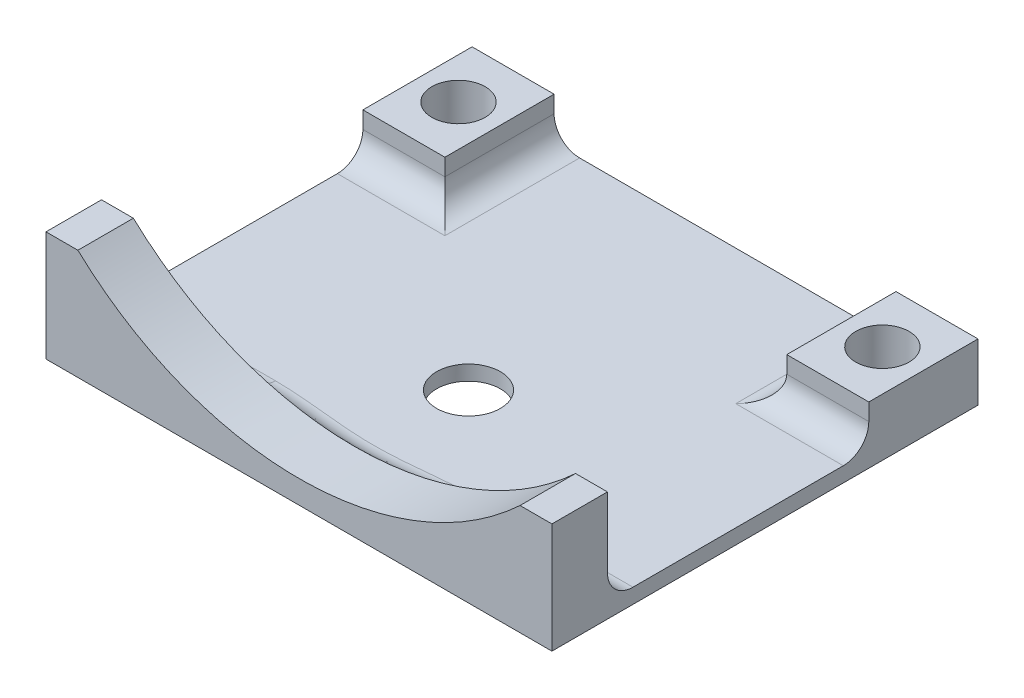
SolidWorks part; units mm, degrees
material "ABS"
ref_plane "Front Plane" through (0, 0, 0) normal (0, 0, 1) x (1, 0, 0)
ref_plane "Top Plane" through (0, 0, 0) normal (0, 1, 0) x (1, 0, 0)
ref_plane "Right Plane" through (0, 0, 0) normal (1, 0, 0) x (0, 0, -1)
sketch "Sketch1" plane through (0, 0, 0) normal (0, 1, 0) x (1, 0, 0)
  line L1 (-22.0091, -18.034) -> (22.0091, -18.034)
  line L2 (-22.0091, -18.034) -> (-22.0091, 18.034)
  line L3 (-22.0091, 18.034) -> (22.0091, 18.034)
  line L4 (22.0091, -18.034) -> (22.0091, 18.034)
  line L5 (-22.0091, -18.034) -> (22.0091, 18.034) construction
  line L6 (-22.0091, 18.034) -> (22.0091, -18.034) construction
  point P0 (0, 0)
  dimension "D1" = 44.0182
  dimension "D2" = 36.068
extrude "Boss-Extrude1" add sketch "Sketch1" along normal blind 1.4859
sketch "Sketch2" plane through (0, 0, 18.034) normal (0, 0, 1) x (1, 0, 0)
  line L0 (-22.0091, 0) -> (-22.0091, 10.9728)
  line L1 (22.0091, 0) -> (22.0091, 10.9728)
  line L2 (-22.0091, 1.4859) -> (22.0091, 1.4859) construction
  line L3 (-22.0091, 2.2987) -> (22.0091, 2.2987) construction
  line L8 (-22.0091, 0) -> (22.0091, 0)
  line L9 (22.0091, 0) -> (22.0091, 1.4859)
  line L10 (22.0091, 1.4859) -> (-22.0091, 1.4859)
  line L11 (-22.0091, 1.4859) -> (-22.0091, 0)
  line L12 (-22.0091, 0) -> (22.0091, 0)
  arc A0 (-22.0091, 10.9728) -> (22.0091, 10.9728) centre (0, 34.558) ccw
  dimension "D2" = 0.8128
  dimension "D1" = 10.9728
  dimension "D3" = 0
extrude "Boss-Extrude2" add sketch "Sketch2" against normal blind 5.5245
hole_wizard "1/4 (0.25) Diameter Hole1" positions "Sketch4" profile "Sketch3" hole size "1/4" standard "ANSI Inch"
sketch "Sketch4" plane through (0, 1.4859, 0) normal (0, 1, 0) x (1, 0, 0)
  line L0 (22.0091, 18.034) -> (-22.0091, 18.034) construction
  point P0 (0, -1.1557)
  dimension "D1" = 19.1897
sketch "Sketch3" plane through (0, 1.4859, 1.1557) normal (1, 0, 0) x (0, 0, 1)
  line L0 (0, 0) -> (0, 11.4327)
  line L1 (0, 11.4327) -> (3.175, 9.525)
  line L2 (3.175, 9.525) -> (3.175, 0)
  line L5 (3.175, 0) -> (0, 0)
  line L10 (0, 11.4327) -> (-3.175, 9.525) construction
  line L11 (0, -6.35) -> (0, 107.95) construction
  dimension "Hole Dia." = 6.35
  dimension "Hole Depth" = 9.525
  dimension "Drill Angle" = 118
sketch "Sketch5" plane through (0, 1.4859, 0) normal (0, 1, 0) x (1, 0, 0)
  line L0 (0, 18.034) -> (0, -18.034) construction
  line L1 (-22.0091, 18.034) -> (-17.018, 18.034)
  line L2 (-22.0091, 18.034) -> (-22.0091, 13.5128)
  line L3 (-22.0091, 13.5128) -> (-17.018, 13.5128)
  line L4 (-17.018, 18.034) -> (-17.018, 13.5128)
  line L5 (22.0091, 18.034) -> (-22.0091, 18.034) construction
  line L6 (-22.0091, -18.034) -> (22.0091, -18.034) construction
  line L7 (17.018, 18.034) -> (17.018, 13.5128)
  line L8 (22.0091, 13.5128) -> (17.018, 13.5128)
  line L9 (22.0091, 18.034) -> (22.0091, 13.5128)
  line L10 (22.0091, 18.034) -> (17.018, 18.034)
  line M4 (22.0091, 18.034) -> (-22.0091, 18.034)
  line M5 (-22.0091, 18.034) -> (-22.0091, -12.5095)
  dimension "D1" = 4.5212
  dimension "D2" = 4.9911
extrude "Boss-Extrude3" add sketch "Sketch5" along normal blind 5.715 from surface at -1.4859 contours L4 L3 M4 M5 | L7 L8 L9 L10 starting at face at (0, 0, -2.0193)
fillet "Fillet1" radius 2.54 5 edges at (19.5135, 1.4859, -13.5128) (17.018, 1.4859, -15.7734) (-17.018, 1.4859, -15.7734) (0, 1.4859, 12.5095) (-19.5136, 1.4859, -13.5128)
sketch "Sketch6" plane through (-22.0091, 0, 0) normal (-1, 0, 0) x (0, 0, 1)
  line L8 (9.9695, 1.4859) -> (-10.9728, 1.4859)
  line L9 (-13.5128, 4.0259) -> (-13.5128, 5.715)
  line L10 (-13.5128, 5.715) -> (-18.034, 5.715)
  line L11 (-18.034, 5.715) -> (-18.034, 0)
  line L12 (-18.034, 0) -> (18.034, 0)
  line L13 (18.034, 0) -> (18.034, 10.9728)
  line L14 (18.034, 10.9728) -> (12.5095, 10.9728)
  line L15 (12.5095, 10.9728) -> (12.5095, 4.0259)
  line L16 (9.9695, 1.4859) -> (-10.9728, 1.4859)
  line L17 (-13.5128, 4.0259) -> (-13.5128, 5.715)
  line L18 (-13.5128, 5.715) -> (-18.034, 5.715)
  line L19 (-18.034, 5.715) -> (-18.034, 0)
  line L20 (-18.034, 0) -> (18.034, 0)
  line L21 (18.034, 0) -> (18.034, 10.9728)
  line L22 (18.034, 10.9728) -> (12.5095, 10.9728)
  line L23 (12.5095, 10.9728) -> (12.5095, 4.0259)
  arc A2 (-13.5128, 4.0259) -> (-10.9728, 1.4859) centre (-10.9728, 4.0259) ccw
  arc A3 (9.9695, 1.4859) -> (12.5095, 4.0259) centre (9.9695, 4.0259) ccw
  arc A4 (-13.5128, 4.0259) -> (-10.9728, 1.4859) centre (-10.9728, 4.0259) ccw
  arc A5 (9.9695, 1.4859) -> (12.5095, 4.0259) centre (9.9695, 4.0259) ccw
  dimension "D1" = 0
extrude "Boss-Extrude4" add sketch "Sketch6" along normal blind 3.175
mirror "Mirror1" about plane through (0, 0, 0) normal (1, 0, 0) of "Boss-Extrude4"
sketch "Sketch9" plane through (0, 0, -18.034) normal (0, 0, -1) x (-1, 0, 0)
  line L8 (14.478, 1.4859) -> (-14.478, 1.4859)
  line L9 (-17.018, 4.0259) -> (-17.018, 5.715)
  line L10 (-17.018, 5.715) -> (-25.1841, 5.715)
  line L11 (-25.1841, 5.715) -> (-25.1841, 0)
  line L12 (-25.1841, 0) -> (25.1841, 0)
  line L13 (25.1841, 0) -> (25.1841, 5.715)
  line L14 (25.1841, 5.715) -> (17.018, 5.715)
  line L15 (17.018, 5.715) -> (17.018, 4.0259)
  line L16 (14.478, 1.4859) -> (-14.478, 1.4859)
  line L17 (-17.018, 4.0259) -> (-17.018, 5.715)
  line L18 (-17.018, 5.715) -> (-25.1841, 5.715)
  line L19 (-25.1841, 5.715) -> (-25.1841, 0)
  line L20 (-25.1841, 0) -> (25.1841, 0)
  line L21 (25.1841, 0) -> (25.1841, 5.715)
  line L22 (25.1841, 5.715) -> (17.018, 5.715)
  line L23 (17.018, 5.715) -> (17.018, 4.0259)
  arc A2 (-17.018, 4.0259) -> (-14.478, 1.4859) centre (-14.478, 4.0259) ccw
  arc A3 (14.478, 1.4859) -> (17.018, 4.0259) centre (14.478, 4.0259) ccw
  arc A4 (-17.018, 4.0259) -> (-14.478, 1.4859) centre (-14.478, 4.0259) ccw
  arc A5 (14.478, 1.4859) -> (17.018, 4.0259) centre (14.478, 4.0259) ccw
  dimension "D1" = 0
extrude "Boss-Extrude5" add sketch "Sketch9" along normal blind 6.35
hole_wizard "#4 (0.209) Diameter Hole1" positions "Sketch11" profile "Sketch10" hole size "#4" standard "ANSI Inch"
sketch "Sketch11" plane through (0, 5.715, 0) normal (0, 1, 0) x (1, 0, 0)
  line L0 (-25.1841, 13.5128) -> (-25.1841, 24.384) construction
  line L1 (-25.1841, 24.384) -> (-17.018, 24.384) construction
  line L2 (17.018, 24.384) -> (25.1841, 24.384) construction
  point P0 (21.1011, 18.9484)
  point P2 (-21.1011, 18.9484)
  point P8 (-25.1841, 18.9484)
  point P12 (-21.1011, 24.384)
  point P16 (21.1011, 24.384)
  dimension "D1" = 42.2021
sketch "Sketch10" plane through (21.1011, 5.715, -18.9484) normal (1, 0, 0) x (0, 0, 1)
  line L0 (0, 0) -> (0, 11.1199)
  line L1 (0, 11.1199) -> (2.6543, 9.525)
  line L2 (2.6543, 9.525) -> (2.6543, 0)
  line L5 (2.6543, 0) -> (0, 0)
  line L10 (0, 11.1199) -> (-2.6543, 9.525) construction
  line L11 (0, -6.35) -> (0, 107.95) construction
  dimension "Hole Dia." = 5.3086
  dimension "Hole Depth" = 9.525
  dimension "Drill Angle" = 118
